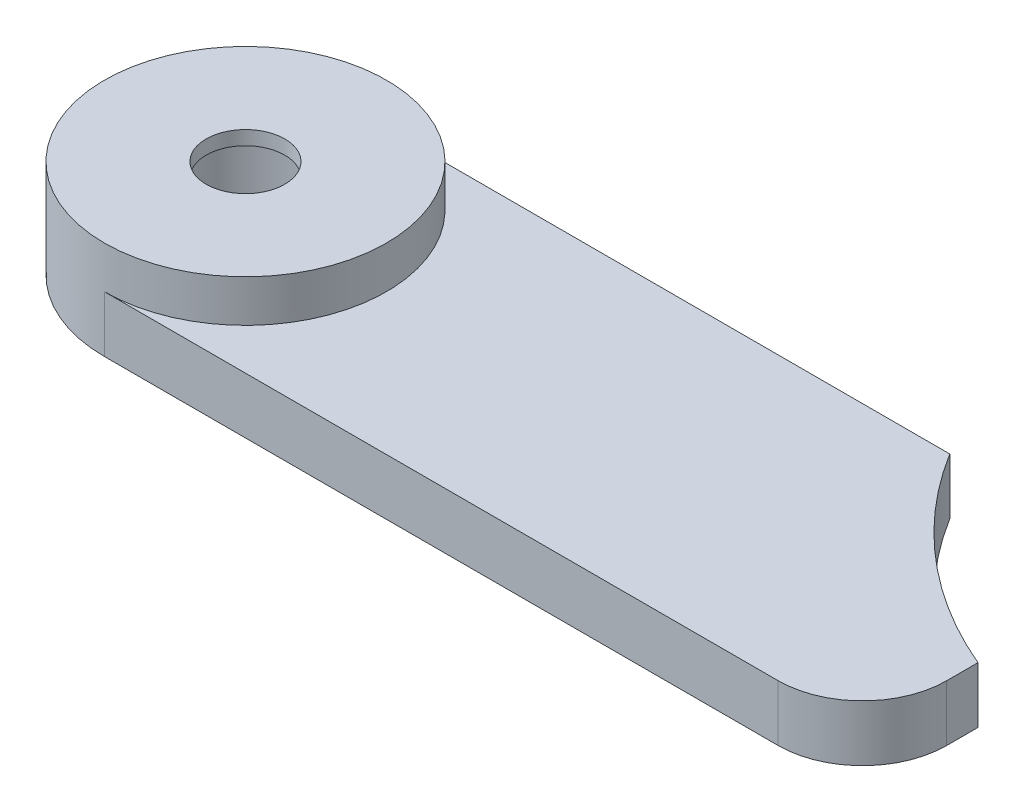
SolidWorks part; units mm, degrees
ref_plane "Front Plane" through (0, 0, 0) normal (0, 0, 1) x (1, 0, 0)
ref_plane "Top Plane" through (0, 0, 0) normal (0, 1, 0) x (1, 0, 0)
ref_plane "Right Plane" through (0, 0, 0) normal (1, 0, 0) x (0, 0, -1)
sketch "Sketch1" plane through (0, 0, 0) normal (0, 1, 0) x (1, 0, 0)
  circle A0 centre (0, 0) radius 2.025
  circle A1 centre (0, 0) radius 5.025
  dimension "D1" = 4.05
  dimension "D2" = 3
extrude "Boss-Extrude1" add sketch "Sketch1" along normal blind 3
sketch "Sketch2" plane through (0, 0, 0) normal (0, -1, 0) x (1, 0, 0)
  line L1 (0, 5.025) -> (27, 5.025)
  line L2 (0, 5.025) -> (0, -5.025)
  line L3 (0, -5.025) -> (27, -5.025)
  line L4 (27, 5.025) -> (27, -5.025)
  circle A0 centre (0, 0) radius 5.025 construction
  circle A1 centre (0, 0) radius 5.025 construction
  dimension "D1" = 27
extrude "Boss-Extrude2" add sketch "Sketch2" against normal blind 2
sketch "Sketch3" plane through (0, 2, 0) normal (0, 1, 0) x (1, 0, 0)
  circle A0 centre (32.8162, 12.9174) radius 15
  dimension "D1" = 30
extrude "Cut-Extrude1" cut sketch "Sketch3" against normal blind 2
fillet "Fillet1" radius 3 1 edges at (27, 1, 5.025)
sketch "Sketch4" plane through (0, 3, 0) normal (0, 1, 0) x (1, 0, 0)
  circle A0 centre (0, 0) radius 2.75
  dimension "D1" = 5.5
extrude "Cut-Extrude2" cut sketch "Sketch4" against normal blind 10
sketch "Sketch5" plane through (0, 3, 0) normal (0, 1, 0) x (1, 0, 0)
  circle A0 centre (0, 0) radius 5.025
extrude "Boss-Extrude3" add sketch "Sketch5" along normal blind 0.5
sketch "Sketch6" plane through (0, 3, 0) normal (0, -1, 0) x (1, 0, 0)
  circle A0 centre (0, 0) radius 1.4
  dimension "D1" = 2.8
extrude "Cut-Extrude3" cut sketch "Sketch6" against normal blind 0.5
